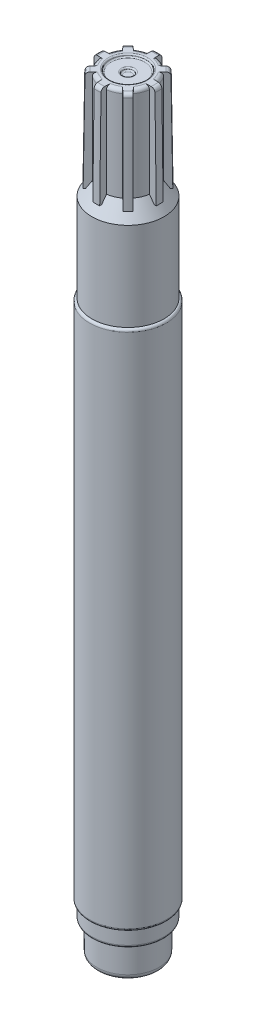
SolidWorks part; units mm, degrees
note: '?' marks a value the reader was unsure of.
ref_plane "Front Plane" through (0, 0, 0) normal (0, 0, 1) x (1, 0, 0)
ref_plane "Top Plane" through (0, 0, 0) normal (0, 1, 0) x (1, 0, 0)
ref_plane "Right Plane" through (0, 0, 0) normal (1, 0, 0) x (0, 0, -1)
ref_axis "Axis1" through (-33.0333, 0, 0) along (1, 0, 0)?
ref_axis "Axis2" through (0, 24.5224, 0) along (0, -1, 0)
ref_axis "Axis3" through (0, 0, -52.9538) along (0, 0, 1)?
sketch "Sketch2" plane through (0, 0, 0) normal (0, 0, 1) x (1, 0, 0)
  line L0 (0, 72.25) -> (0, -72.25)
  line L1 (0, -72.25) -> (5.83, -72.25)
  line L2 (5.83, -72.25) -> (5.83, -66.25)
  line L3 (5.83, -66.25) -> (6.785, -66.25)
  line L4 (6.785, -66.25) -> (6.785, 51.55)
  line L5 (6.785, 51.55) -> (4.8, 54.55)
  line L6 (4.8, 54.55) -> (4.8, 72.25)
  line L7 (4.8, 72.25) -> (0, 72.25)
  point P2 (0, 0)
  point P6 (5.83, 53.1917)
  point P11 (6.6772, 52.5496)
  point P12 (4.8, 51.7328)
  dimension "D1" = 144.5
  dimension "D2" = 5.83
  dimension "D3" = 6.785
  dimension "D4" = 17.7
  dimension "D5" = 6
  dimension "D6" = 4.8
  dimension "D7" = 20.7
revolve "Revolve1" add sketch "Sketch2" angle 360 about L0
fillet "Fillet1" radius 0.475 2 edges at (-5.83, -66.25, 0) (-6.785, -66.25, 0)
ref_plane "Plane1" through (0, 53.25, 0) normal (0, 1, 0) x (1, 0, 0)
sketch "Sketch4" plane through (0, 72.25, 0) normal (0, 1, 0) x (1, 0, 0)
  line L0 (4.7487, 0.7) -> (5.7131, 0.65)
  line L1 (5.7131, -0.65) -> (4.7487, -0.7)
  line L2 (0, 0) -> (5.75, 0) construction
  arc A0 (4.7487, 0.7) -> (4.7487, -0.7) centre (0, 0) cw
  circle A1 centre (0, 0) radius 4.8 construction
  arc A2 (5.7131, 0.65) -> (5.7131, -0.65) centre (0, 0) cw
  point P8 (0, 0)
  point P10 (0, 0)
  point P11 (0, 0)
  point P12 (4.5578, -1.5054)
  point P13 (4.8, 0)
  point P14 (5.4091, 0.5087)
  point P15 (0, 0)
  point P16 (4.701, 0.9696)
  dimension "D1" = 5.75
  dimension "D2" = 1.3
  dimension "D3" = 1.4
sketch "Sketch5" plane through (0, 53.25, 0) normal (0, 1, 0) x (1, 0, 0)
  line L0 (4.7487, 0.7) -> (5.9647, 0.65)
  line L1 (5.9647, -0.65) -> (4.7487, -0.7)
  line L2 (0, 0) -> (6, 0) construction
  arc A0 (4.7487, 0.7) -> (4.7487, -0.7) centre (0, 0) cw
  arc A1 (5.9647, -0.65) -> (5.9647, 0.65) centre (0, 0) ccw
  dimension "D1" = 1.3
  dimension "D2" = 6
loft "Loft1" add profiles "Sketch4", "Sketch5"
pattern_circular "CirPattern1" count 8 every 45 about axis through (0, 24.5224, 0) along (0, -1, 0) of bodies 152
combine bodies "Combine1" bodies to combine 151 152 153 154 155 156 157 158 159
fillet "Fillet2" radius 0.687 48 edges
sketch "Sketch6" plane through (0, 72.25, 0) normal (0, 1, 0) x (1, 0, 0)
  circle A0 centre (0, 0) radius 3.43
  dimension "D1" = 6.86
extrude "Cut-Extrude1" cut sketch "Sketch6" against normal blind 0.5
sketch "Sketch7" plane through (0, 71.75, 0) normal (0, 1, 0) x (1, 0, 0)
  circle A0 centre (0, 0) radius 1
  dimension "D1" = 2
extrude "Cut-Extrude2" cut sketch "Sketch7" against normal blind 0.5
fillet "Fillet3" radius 0.25 4 edges at (-3.43, 71.75, 0) (-3.43, 72.25, 0) (-1, 71.25, 0) (-1, 71.75, 0)
fillet "Fillet4" radius 1 1 edges at (-5.83, -72.25, 0)
sketch "Sketch8" plane through (0, 0, 0) normal (0, 0, 1) x (1, 0, 0)
  line L0 (6.785, 34.9) -> (7.215, 34.9)
  line L1 (6.785, -65.775) -> (6.785, 51.55) construction
  line L2 (7.215, 34.9) -> (7.215, -63.25)
  line L3 (7.215, -63.25) -> (6.785, -63.25)
  line L4 (6.785, -63.25) -> (6.785, 34.9)
  line L6 (-4.83, -72.25) -> (4.83, -72.25) construction
  dimension "D1" = 7.215
  dimension "D2" = 98.15
  dimension "D3" = 9
revolve "Revolve2" add sketch "Sketch8" angle 360 about axis through (0, 24.5224, 0) along (0, -1, 0)
fillet "Fillet5" radius 0.475 2 edges at (0, -63.25, 7.215) (0, 34.9, 7.215)
